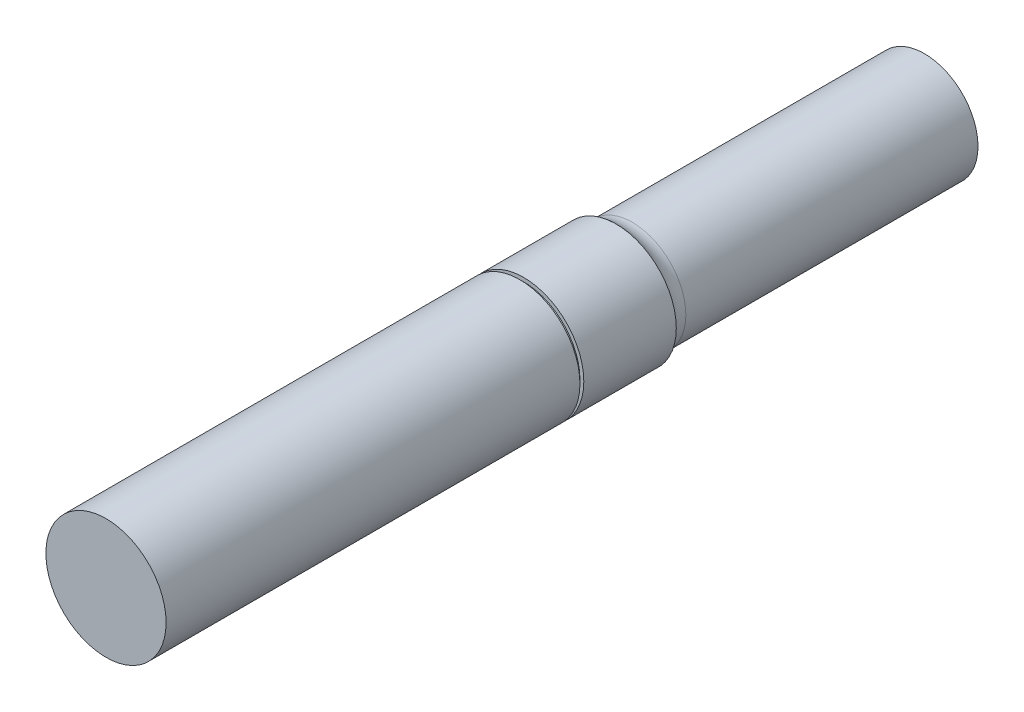
SolidWorks part; units mm, degrees
material "O1 Steel"
ref_plane "Alzado" through (0, 0, 0) normal (0, 0, 1) x (1, 0, 0)
ref_plane "Planta" through (0, 0, 0) normal (0, 1, 0) x (1, 0, 0)
ref_plane "Vista lateral" through (0, 0, 0) normal (1, 0, 0) x (0, 0, -1)
sketch "Croquis1" plane through (0, 0, 0) normal (1, 0, 0) x (0, 0, -1)
  line L0 (-127, 0) -> (127, 0) construction
  line L1 (-13.4874, 0) -> (-13.4874, 1.9812)
  line L2 (-13.4874, 1.9812) -> (0.1524, 1.9812)
  line L3 (0.1524, 1.9812) -> (0.1524, 1.8542)
  line L4 (0.1524, 1.8542) -> (0.2794, 1.8542)
  line L5 (0.2794, 1.8542) -> (0.2794, 1.9812)
  line L10 (0.2794, 1.9812) -> (3.3274, 1.9812)
  line L11 (3.3274, 1.9812) -> (3.3274, 1.7653)
  line L12 (3.3274, 1.7653) -> (13.4874, 1.7653)
  line L13 (13.4874, 1.7653) -> (13.4874, 0)
  line L14 (13.4874, 0) -> (-13.4874, 0)
  point P7 (0, 4.1447)
  point P10 (0.1744, 1.9812)
  point P11 (0, 1.5618)
  point P12 (0, 0)
  point P13 (0.2794, 1.6943)
  point P18 (2.6433, 2.6678)
  point P19 (30.5028, 4.0105)
  point P20 (4.1202, 1.0567)
  point P21 (20.8359, 8.1055)
  point P22 (0.8611, 1.9812)
  point P23 (1.5302, 1.0567)
  point P24 (2.2311, 1.104)
  point P25 (9.3051, 1.7653)
  point P26 (1.406, 1.6751)
  point P27 (1.7224, 1.9812)
  point P28 (0.3382, 1.9812)
  point P29 (1.5543, 1.6158)
  dimension "D1" = 254
  dimension "D2" = 3.9624
  dimension "D3" = 26.9748
  dimension "D4" = 3.5306
  dimension "D5" = 10.16
  dimension "D6" = 3.048
  dimension "D7" = 0.127
  dimension "D8" = 0.127
revolve "Revolución1" add sketch "Croquis1" angle 360 about L0
fillet "Redondeo1" radius 0.762 1 edges at (1.7653, 0, -3.3274)
sketch "Croquis2" plane through (0, 0, -13.4874) normal (0, 0, -1) x (-1, 0, 0)
  point P0 (0, 0)
hole_wizard "Taladro de margen para #101" positions "Croquis2" profile "Croquis3" hole size "#10" standard "Ansi Inch"
sketch "Croquis3" plane through (0, 0, -13.4874) normal (1, 0, 0) x (0, 1, 0)
  line L0 (0, 0) -> (0, 1.5678)
  line L1 (0, 1.5678) -> (0.7493, 1.1176)
  line L2 (0.7493, 1.1176) -> (0.7493, 0)
  line L5 (0.7493, 0) -> (0, 0)
  line L10 (0, 1.5678) -> (-0.7493, 1.1176) construction
  line L11 (0, -6.35) -> (0, 107.95) construction
  dimension "Diámetro de taladro" = 1.4986
  dimension "Profundidad de taladro" = 1.1176
  dimension "Ángulo de perforador" = 118
chamfer "Chaflán1" distance 0.8382 angle 30 1 edges at (-0.7493, 0, -13.4874) first distance on face at (-0.7493, 0, -13.4874)
